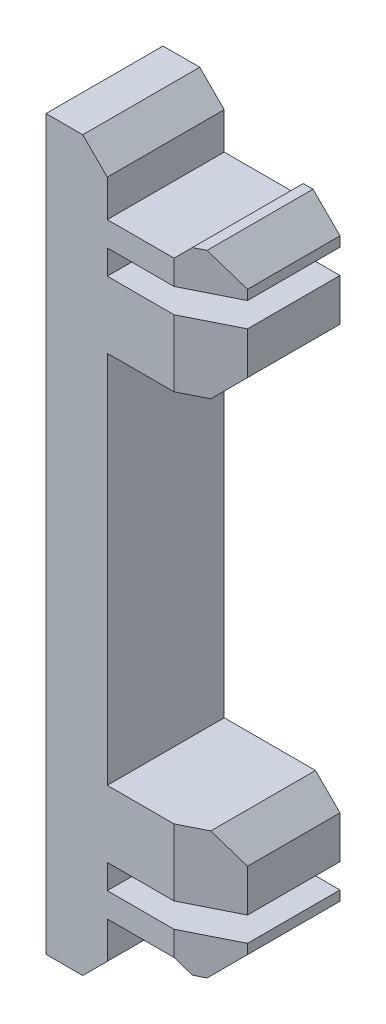
SolidWorks part; units mm, degrees
ref_plane "Front Plane" through (0, 0, 0) normal (0, 0, 1) x (1, 0, 0)
ref_plane "Top Plane" through (0, 0, 0) normal (0, 1, 0) x (1, 0, 0)
ref_plane "Right Plane" through (0, 0, 0) normal (1, 0, 0) x (0, 0, -1)
sketch "Sketch1" plane through (0, 0, 0) normal (0, 0, 1) x (1, 0, 0)
  line L0 (-1.4125, 9.7) -> (3.3175, 9.7)
  line L1 (-4.5875, -18.875) -> (4.5875, -18.875) construction
  line L2 (-4.5875, -18.875) -> (-4.5875, 18.875) construction
  line L3 (-4.5875, 18.875) -> (4.5875, 18.875) construction
  line L4 (4.5875, -18.875) -> (4.5875, 18.875) construction
  line L5 (-4.5875, -18.875) -> (4.5875, 18.875) construction
  line L6 (-4.5875, 18.875) -> (4.5875, -18.875) construction
  line L7 (-2.6825, -18.875) -> (-4.5875, -18.875)
  line L8 (-1.4125, -17.605) -> (-1.4125, 17.605)
  line L9 (-2.6825, 18.875) -> (-4.5875, 18.875)
  line L10 (-4.5875, -18.875) -> (-4.5875, 18.875)
  line L11 (-1.4125, -18.875) -> (-4.5875, 18.875) construction
  line L12 (-1.4125, 18.875) -> (-4.5875, -18.875) construction
  line L13 (4.5875, 9.7) -> (-1.4125, 9.7) construction
  line L14 (4.5875, 9.7) -> (4.5875, 15.7) construction
  line L15 (4.5875, 15.7) -> (-1.4125, 15.7) construction
  line L16 (-1.4125, 9.7) -> (-1.4125, 15.7) construction
  line L17 (4.5875, 9.7) -> (-1.4125, 15.7) construction
  line L18 (4.5875, 15.7) -> (-1.4125, 9.7) construction
  line L19 (4.5875, -15.7) -> (-1.4125, -15.7) construction
  line L20 (4.5875, -15.7) -> (4.5875, -9.7) construction
  line L21 (4.5875, -9.7) -> (-1.4125, -9.7) construction
  line L22 (-1.4125, -15.7) -> (-1.4125, -9.7) construction
  line L23 (4.5875, -15.7) -> (-1.4125, -9.7) construction
  line L24 (4.5875, -9.7) -> (-1.4125, -15.7) construction
  line L25 (4.5875, 10.97) -> (4.5875, 13.16)
  line L26 (4.5875, 13.16) -> (-1.4125, 13.16)
  line L27 (-1.4125, 15.7) -> (2.0475, 15.7)
  line L28 (2.0475, 15.7) -> (2.6825, 16.335)
  line L29 (2.6825, 16.335) -> (3.1905, 16.335)
  line L30 (3.1905, 16.335) -> (4.5875, 14.938)
  line L31 (4.5875, 14.938) -> (4.5875, 14.43)
  line L32 (4.5875, 14.43) -> (-1.4125, 14.43)
  line L33 (0, 0) -> (4.5875, 0) construction
  line L34 (3.3175, 9.7) -> (4.5875, 10.97)
  line L35 (3.3175, 9.7) -> (4.5875, 9.7) construction
  line L36 (4.5875, 9.7) -> (4.5875, 10.97) construction
  line L37 (-2.6825, 18.875) -> (-1.4125, 17.605)
  line L38 (-2.6825, -18.875) -> (-1.4125, -17.605)
  line L39 (-1.4125, 18.875) -> (-2.6825, 18.875) construction
  line L40 (-1.4125, 17.605) -> (-1.4125, 18.875) construction
  line L41 (-1.4125, -18.875) -> (-2.6825, -18.875) construction
  line L42 (-1.4125, -18.875) -> (-1.4125, -17.605) construction
  point P0 (0, 0)
  point P6 (-3, 0)
  point P7 (1.5875, -12.7)
  point P10 (1.5875, 12.7)
  point P29 (0.3175, 15.7)
  dimension "D1" = 3.175
  dimension "D2" = 6
  dimension "D3" = 6
  dimension "D4" = 25.4
  dimension "D5" = 45
  dimension "D6" = 45
  dimension "D7" = 0.508
  dimension "D9" = 0.635
  dimension "D10" = 1.27
  dimension "D11" = 0.762
  dimension "D12" = 1.27
  dimension "D13" = 3.175
  dimension "D14" = 1.27
  dimension "D15" = 1.27
  dimension "D16" = 45
  dimension "D17" = 1.27
  dimension "D8" = 6
extrude "Boss-Extrude1" add sketch "Sketch1" along normal mid plane 6.065 contours L8 L37 L9 L10 L7 L38
extrude "Boss-Extrude2" add sketch "Sketch1<3>" along normal up to surface and the other way up to surface contours L32 L31 L30 L29 L28 L27 L8 | L25 L26 L8 L0 region at (1.4834, 11.4828, 0) region at (1.6101, 15.1318, 0) up to face at (-2.8942, 0, 3.0325) other way up to face at (-2.8942, 0, -3.0325)
sketch "Sketch1<3>" plane through (0, 0, 0) normal (0, 0, 1) x (1, 0, 0) same geometry as "Sketch1"
sketch "Sketch2" plane through (0, 9.7, 0) normal (0, -1, 0) x (1, 0, 0)
  line L0 (2.0475, 3.0325) -> (4.5875, 1.7625)
  line L1 (3.3175, 3.0325) -> (-1.4125, 3.0325) construction
  line L2 (4.5875, 3.0325) -> (4.5875, -3.0325) construction
  line L3 (4.5875, 1.7625) -> (4.5875, 3.0325)
  line L4 (4.5875, 3.0325) -> (2.0475, 3.0325)
  dimension "D1" = 2.54
  dimension "D2" = 1.27
extrude "Cut-Extrude1" cut sketch "Sketch2" against normal through all
mirror "Mirror2" about plane through (0, 0, 0) normal (0, 1, 0) of bodies 104
equation "\"D1@Boss-Extrude1\"=.5in-6mm-.025in"
equation "\"D8@Sketch1\"=6mm"
